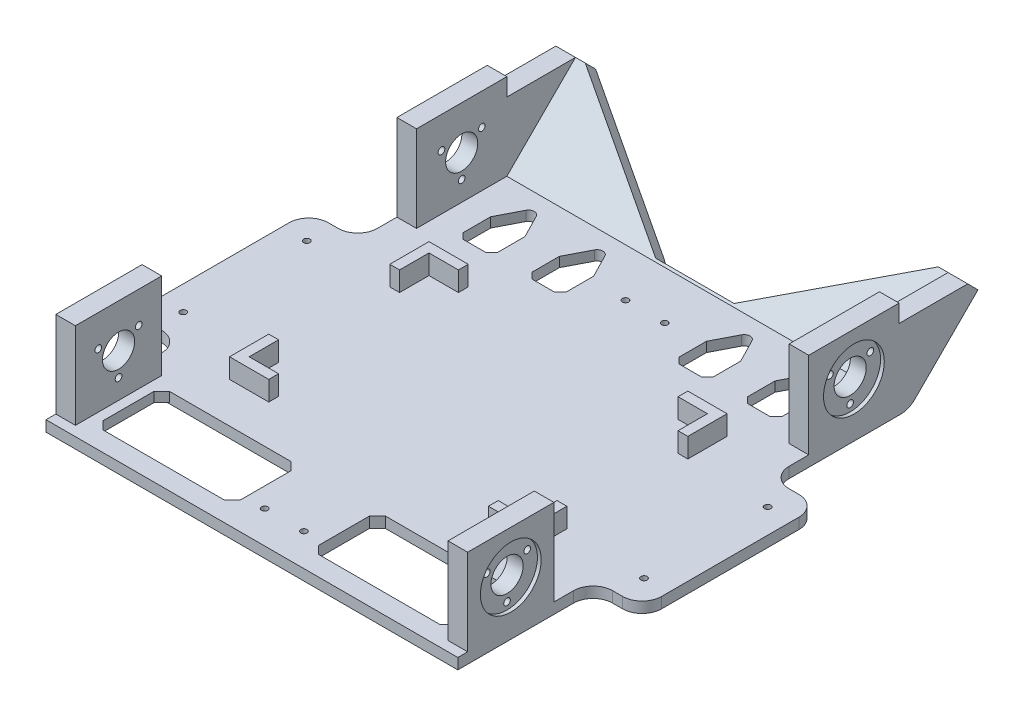
SolidWorks part; units mm, degrees
ref_plane "前视基准面" through (0, 0, 0) normal (0, 0, 1) x (1, 0, 0)
ref_plane "上视基准面" through (0, 0, 0) normal (0, 1, 0) x (1, 0, 0)
ref_plane "右视基准面" through (0, 0, 0) normal (1, 0, 0) x (0, 0, -1)
sketch "草图1" plane through (0, 0, 0) normal (0, 1, 0) x (1, 0, 0)
  line L0 (0, 0) -> (210, 0)
  line L1 (210, 0) -> (210, -230)
  line L2 (210, -230) -> (0, -230)
  line L3 (0, -230) -> (0, 0)
  line L4 (0, 0) -> (3, 0)
  line L5 (0, 0) -> (5, 0)
  line L6 (5, 0) -> (5, -230)
  line L7 (210, 0) -> (205, 0)
  line L8 (205, 0) -> (205, -230)
  line L9 (0, 0) -> (0, -10)
  line L10 (0, -10) -> (210, -10)
  line L11 (210, -230) -> (210, -220)
  line L12 (210, -220) -> (0, -220)
  line L13 (5, -10) -> (85, -10)
  line L14 (85, -10) -> (85, -44)
  line L15 (85, -44) -> (5, -44)
  line L16 (205, -10) -> (125, -10)
  line L17 (125, -10) -> (125, -44)
  line L18 (125, -44) -> (205, -44)
  line L19 (5, -220) -> (5, -186)
  line L20 (5, -186) -> (85, -186)
  line L21 (85, -186) -> (85, -220)
  line L22 (85, -220) -> (5, -220)
  line L23 (205, -220) -> (125, -220)
  line L24 (125, -220) -> (125, -186)
  line L25 (125, -186) -> (205, -186)
  line L26 (205, -186) -> (205, -220)
  line L27 (5, -10) -> (5, -44)
  line L28 (205, -44) -> (205, -10)
extrude "凸台-拉伸1" add sketch "草图1" along normal blind 5.5 contours L24 L25 L8 L18 L17 L10 L14 L15 L6 L20 L21 L12 | L3 L10 L6 L0 | L12 L6 L10 L3 | L6 L10 L8 L0 | L12 L1 L10 L8 | L8 L10 L1 L0 | L8 L12 L6 L2 | L6 L12 L3 L2 | L1 L12 L8 L2 region at (2.5, 0, 5) region at (2.5, 0, 115) region at (105, 0, 5) region at (2.5, 0, 225) region at (207.5, 0, 5) region at (105, 0, 225) region at (105, 0, 115) region at (207.5, 0, 115) region at (207.5, 0, 225)
sketch "草图3" plane through (0, 5.5, 0) normal (0, 1, 0) x (1, 0, 0)
  line L0 (85, -10) -> (85, 0)
  line L1 (0, 0) -> (210, 0) construction
  line L2 (85, 0) -> (85, -5)
  line L3 (85, -5) -> (0, -5)
  line L4 (0, -230) -> (0, 0) construction
  line L5 (0, -5) -> (0, -46.0662)
  line L6 (0, -46.0662) -> (0, -51.0662)
  line L7 (0, -51.0662) -> (5, -51.0662)
  line L8 (5, -51.0662) -> (5, -5)
  line L9 (105, 0) -> (105, -230)
  line L10 (210, -230) -> (0, -230) construction
  line L11 (5, -220) -> (5, -225)
  line L12 (5, -225) -> (0, -225)
  line L13 (0, -225) -> (0, -181)
  line L14 (0, -181) -> (5, -181)
  line L15 (5, -181) -> (5, -220)
  line L16 (210, -181) -> (205, -181)
  line L17 (210, -225) -> (210, -181)
  line L18 (205, -225) -> (210, -225)
  line L19 (205, -220) -> (205, -225)
  line L20 (205, -181) -> (205, -220)
  line L21 (5, -5) -> (5, -51.0662)
  line L22 (0, -51.0662) -> (0, -5)
  line L23 (210, -46.0662) -> (210, -51.0662)
  line L24 (210, -51.0662) -> (205, -51.0662)
  line L25 (205, -51.0662) -> (205, -5)
  line L26 (210, -5) -> (210, -46.0662)
  line L27 (205, -5) -> (210, -5)
extrude "凸台-拉伸2" add sketch "草图3" along normal blind 44 contours L7 L8 L17 L3 L10 | L15 L14 L10 L12 L11 L26 | L16 L20 L6 L19 L18 L2 | L27 L25 L22 L24 L2 region at (2.5, 5.5, 28.0331) region at (2.5, 5.5, 203) region at (207.5, 5.5, 203) region at (207.5, 5.5, 28.0331)
sketch "草图4" plane through (0, 0, 0) normal (-1, 0, 0) x (0, 0, 1)
  line L0 (5, 49.5) -> (51.0662, 5.5)
  line L1 (181, 49.5) -> (225, 5.5)
  circle A1 centre (203, 27.5) radius 17
  circle A2 centre (28.0331, 27.5) radius 15
  circle A3 centre (28.0331, 27.5) radius 8.2
  circle A4 centre (28.0331, 27.5) radius 11.9
  circle A5 centre (28.0331, 15.6) radius 1.7
  circle A6 centre (17.7274, 33.45) radius 1.7
  circle A7 centre (38.3388, 33.45) radius 1.7
  point P24 (28.0331, 27.5)
  dimension "D1" = 3
extrude "切除-拉伸1" cut sketch "草图4" against normal through all both and the other way through all contours A4 A6 | A4 A6 | A4 A7 | A4 A7 | A4 A5 | A4 A5 | L0 A3 | L0 A3 region at (0, 30.0167, 30.4369) region at (0, 24.9833, 25.6293) region at (0, 33.7996, 38.9443) region at (0, 33.0785, 37.6954) region at (0, 33.0785, 18.3708) region at (0, 33.7996, 17.1219) region at (0, 14.9008, 28.0331) region at (0, 16.3429, 28.0331)
sketch "草图5" plane through (0, 0, 0) normal (-1, 0, 0) x (0, 0, 1)
  circle A1 centre (28.0331, 27.5) radius 15.5
extrude "切除-拉伸3" cut sketch "草图5" against normal blind 1.9
sketch "草图6" plane through (210, 0, 0) normal (1, 0, 0) x (0, 0, -1)
  circle A0 centre (-28.0331, 27.5) radius 15.5
extrude "切除-拉伸4" cut sketch "草图6" against normal blind 1.9
sketch "草图7" plane through (0, 0, 0) normal (-1, 0, 0) x (0, 0, 1)
  line L0 (181, 49.5) -> (225, 5.5)
  line L1 (203, 27.5) -> (203, 15.6)
  circle A0 centre (203, 27.5) radius 11.9
  circle A1 centre (203, 27.5) radius 8.2
  circle A2 centre (203, 15.6) radius 1.7
  circle A3 centre (192.6943, 33.45) radius 1.7
  circle A4 centre (213.3057, 33.45) radius 1.7
  point P15 (203, 27.5)
  dimension "D1" = 3
extrude "切除-拉伸5" cut sketch "草图7" against normal through all both and the other way through all contours A0 A3 | A0 A3 | A0 A4 | A0 A4 | A0 A2 L1 | L1 A2 A0 | A0 A2 | L0 A1 | L0 A1 L1 | L1 A1 L0 region at (0, 29.9609, 205.4609) region at (0, 25.8594, 199.0393) region at (0, 33.7996, 213.9112) region at (0, 33.0785, 212.6623) region at (0, 33.0785, 193.3377) region at (0, 33.7996, 192.0888) region at (0, 22.5783, 205.0386) region at (0, 16.3429, 203.7042) region at (0, 16.3429, 202.2958) region at (0, 14.9008, 203)
sketch "草图8" plane through (0, 0, 0) normal (-1, 0, 0) x (0, 0, 1)
  circle A0 centre (203, 27.5) radius 15.5
extrude "切除-拉伸6" cut sketch "草图8" against normal blind 1.9
sketch "草图9" plane through (210, 0, 0) normal (1, 0, 0) x (0, 0, -1)
  circle A0 centre (-203, 27.5) radius 15.5
extrude "切除-拉伸7" cut sketch "草图9" against normal blind 1.9
sketch "草图10" plane through (0, 5.5, 0) normal (0, 1, 0) x (1, 0, 0)
  line L0 (5, -10) -> (15, -10)
  line L1 (5, -10) -> (85, -10) construction
  line L2 (15, -10) -> (15, -220)
  line L3 (85, -220) -> (5, -220) construction
  line L4 (15, -220) -> (5, -220)
  line L5 (5, -220) -> (5, -186)
  line L6 (5, -181) -> (5, -225) construction
  line L7 (5, -181) -> (5, -186) construction
  line L8 (5, -186) -> (15, -186)
  line L9 (5, -186) -> (85, -186) construction
  line L10 (5, -10) -> (5, -44)
  line L11 (5, -44) -> (15, -44)
  line L12 (85, -44) -> (5, -44) construction
  line L13 (205, -10) -> (195, -10)
  line L14 (125, -10) -> (205, -10) construction
  line L15 (195, -10) -> (195, -220)
  line L16 (205, -220) -> (125, -220) construction
  line L17 (195, -220) -> (205, -220)
  line L18 (205, -220) -> (205, -186)
  line L19 (205, -186) -> (195, -186)
  line L20 (125, -186) -> (205, -186) construction
  line L21 (205, -10) -> (205, -44)
  line L22 (205, -44) -> (195, -44)
  line L23 (125, -44) -> (205, -44) construction
  line M7 (5, -10) -> (85, -10)
  line M9 (85, -44) -> (5, -44)
  line M15 (5, -186) -> (85, -186)
  line M17 (85, -220) -> (5, -220)
  line M25 (205, -220) -> (125, -220)
  line M27 (125, -186) -> (205, -186)
  line M33 (205, -44) -> (125, -44)
  line M35 (125, -10) -> (205, -10)
extrude "凸台-拉伸3" add sketch "草图10" against normal blind 5 contours L21 L15 M35 M33 | L10 L2 M7 M9 | L5 L2 M17 M15 | L18 L15 M25 M27 region at (10, 5.5, 203) region at (10, 5.5, 27) region at (200, 5.5, 27) region at (200, 5.5, 203)
sketch "草图11" plane through (0, 5.5, 0) normal (0, 1, 0) x (1, 0, 0)
  line L0 (15, -10) -> (5, -10)
  line L1 (5, -51.0662) -> (5, -5) construction
  line L2 (10, -10) -> (10, -51.0662)
  line L3 (10, -51.0662) -> (5, -51.0662)
  line L4 (5, -51.0662) -> (5, -5)
  line L5 (5, -5) -> (10, -5)
  line L6 (10, -5) -> (10, -10)
  line L7 (10, -51.0662) -> (10, -230)
  line L8 (210, -230) -> (0, -230) construction
  line L9 (5, -225) -> (10, -225)
  line L10 (5, -181) -> (10, -181)
  line L11 (10, -181) -> (10, -225)
  line L12 (5, -181) -> (5, -225)
  line L13 (195, -10) -> (205, -10)
  line L14 (205, -51.0662) -> (205, -5) construction
  line L15 (200, -10) -> (200, -51.0662)
  line L16 (200, -51.0662) -> (205, -51.0662)
  line L17 (205, -51.0662) -> (205, -5)
  line L18 (205, -5) -> (200, -5)
  line L19 (200, -5) -> (200, -10)
  line L20 (200, -225) -> (205, -225)
  line L21 (205, -225) -> (205, -181)
  line L22 (205, -181) -> (200, -181)
  line L23 (200, -181) -> (200, -225)
  line M6 (5, -181) -> (5, -225)
  line M12 (205, -225) -> (205, -181)
  line M16 (205, -51.0662) -> (205, -5)
  line M22 (5, -5) -> (5, -51.0662)
extrude "凸台-拉伸4" add sketch "草图11" along normal blind 44 contours L3 L2 L0 M22 | L6 L5 L0 M22 | L18 L19 L13 M16 | L15 L16 L13 M16 | L10 L9 L7 M6 | L22 L23 L20 M12 region at (7.5, 5.5, 30.5331) region at (7.5, 5.5, 203) region at (7.5, 5.5, 7.5) region at (202.5, 5.5, 7.5) region at (202.5, 5.5, 30.5331) region at (202.5, 5.5, 203)
sketch "草图12" plane through (1.9, 0, 0) normal (-1, 0, 0) x (0, 0, 1)
  circle A0 centre (17.7274, 33.45) radius 1.7
  circle A1 centre (38.3388, 33.45) radius 1.7
  circle A2 centre (28.0331, 15.6) radius 1.7
  circle A3 centre (28.0331, 27.5) radius 8.2
  circle A4 centre (192.6943, 33.45) radius 1.7
  circle A5 centre (213.3057, 33.45) radius 1.7
  circle A6 centre (203, 15.6) radius 1.7
  circle A7 centre (203, 27.5) radius 8.2
extrude "切除-拉伸8" cut sketch "草图12" against normal through all both and the other way through all
sketch "草图13" plane through (210, 0, 0) normal (1, 0, 0) x (0, 0, -1)
  line L0 (-5, 5.5) -> (14.6466, 25.1466)
sketch "草图15" plane through (210, 0, 0) normal (1, 0, 0) x (0, 0, -1)
  line L0 (-5, 5.5) -> (-5, 40.5)
  line L1 (-5, 49.5) -> (-5, 5.5) construction
  line L2 (-5, 40.5) -> (31.0178, 40.5)
ref_plane "基准面5" through (0, 5.25, 5.25) normal (0, 0.7071, 0.7071) x (1, 0, 0)
sketch "草图17" plane through (0, 5.25, 5.25) normal (0, 0.7071, 0.7071) x (1, 0, 0)
  line L0 (210, 0.3536) -> (210, 49.8474)
  line L1 (210, 49.8474) -> (0, 49.8474)
  line L2 (0, 49.8474) -> (0, 0.3536)
  line L3 (0, 0.3536) -> (210, 0.3536)
extrude "凸台-拉伸5" add sketch "草图17" against normal through all
sketch "草图18" plane through (0, 0, 0) normal (-1, 0, 0) x (0, 0, 1)
  line L0 (-29.9975, 40.4975) -> (5, 40.5)
  line L1 (5, 40.5) -> (5, 5.5)
  line L2 (5, 5.5) -> (-29.9975, 40.4975)
extrude "凸台-拉伸6" add sketch "草图18" against normal blind 10
sketch "草图19" plane through (210, 0, 0) normal (1, 0, 0) x (0, 0, -1)
  line L0 (30, 40.5) -> (-5, 40.5)
  line L1 (-5, 40.5) -> (31.0178, 40.5) construction
  line L2 (40.3406, 50.8406) -> (-50.8406, -40.3406) construction
  line L3 (-5, 40.5) -> (-5, 5.5)
  line L4 (-5, 5.5) -> (30, 40.5)
extrude "凸台-拉伸8" add sketch "草图19" against normal blind 10
sketch "草图20" plane through (0, 5.25, 5.25) normal (0, 0.7071, 0.7071) x (1, 0, 0)
  line L0 (15, -3.182) -> (15, 49.8474)
  line L1 (200, 49.8474) -> (10, 49.8474) construction
  line L4 (125, 49.8474) -> (85, 49.8474)
  line L5 (85, 1.6082) -> (125, 1.6082)
  line L6 (125, 1.6082) -> (125, 49.8474)
  line L7 (85, 49.8474) -> (125, 49.8474)
  line L8 (85, 1.6082) -> (85, 49.8474)
  line L9 (15, 49.8474) -> (85, 1.6082)
  line L10 (195, -3.182) -> (195, 49.8474)
  line L11 (195, 49.8474) -> (125, 1.6082)
  line L12 (15, 1.6082) -> (85, 1.6082)
  line L13 (125, 1.6082) -> (195, 1.6082)
  line L14 (195, 1.6082) -> (195, 49.8474)
  line M4 (200, 49.8474) -> (10, 49.8474)
extrude "切除-拉伸9" cut sketch "草图20" against normal blind 10 contours L9 L8 M4 | L8 L5 L6 M4 | L11 L6 M4 region at (61.6667, 29.1274, -18.6274) region at (105, 23.4423, -12.9423) region at (148.3333, 29.1274, -18.6274)
sketch "草图21" plane through (0, 5.5, 0) normal (0, 1, 0) x (1, 0, 0)
  line L1 (15, -10) -> (85, -10) construction
  line L4 (125, -10) -> (195, -10) construction
  line L6 (32.5, -10) -> (15, -44)
  line L7 (32.5, -10) -> (50, -44)
  line L8 (85, -44) -> (15, -44) construction
  line L9 (50, -44) -> (67.5, -10)
  line L10 (67.5, -10) -> (85, -44)
  line L11 (125, -44) -> (142.5, -10)
  line L12 (142.5, -10) -> (160, -44)
  line L14 (160, -44) -> (177.5, -10)
  line L15 (177.5, -10) -> (195, -44)
  line L16 (15, -44) -> (15, -10)
  line L17 (15, -10) -> (32.5, -10)
  line L18 (32.5, -10) -> (67.5, -10)
  line L19 (67.5, -10) -> (85, -10)
  line L20 (85, -10) -> (85, -44)
  line L21 (125, -44) -> (125, -10)
  line L22 (125, -10) -> (142.5, -10)
  line L23 (142.5, -10) -> (177.5, -10)
  line L24 (177.5, -10) -> (195, -10)
  line L25 (195, -10) -> (195, -44)
  line L26 (41.25, -27) -> (41.25, -44)
  line L27 (58.75, -27) -> (58.75, -44)
  line L28 (151.25, -27) -> (151.25, -44)
  line L29 (125, -44) -> (195, -44) construction
  line L30 (168.75, -27) -> (168.75, -44)
  line L31 (41.25, -44) -> (58.75, -44)
  line L32 (151.25, -44) -> (168.75, -44)
  line M21 (15, -44) -> (15, -10)
  line M22 (15, -10) -> (85, -10)
  line M23 (85, -10) -> (85, -44)
  line M24 (85, -44) -> (15, -44)
  line M29 (125, -10) -> (195, -10)
  line M30 (195, -10) -> (195, -44)
  line M31 (195, -44) -> (125, -44)
  line M32 (125, -44) -> (125, -10)
extrude "凸台-拉伸11" add sketch "草图21" against normal blind 5 contours L6 M22 M21 | L7 L9 M22 | L7 L26 M24 | L27 L9 M24 | L10 M22 M23 | L11 M32 M29 | L12 L14 M29 | L15 M29 M30 | L30 L14 M31 | L12 L28 M31 region at (50, 5.5, 21.3333) region at (20.8333, 5.5, 21.3333) region at (44.1667, 5.5, 38.3333) region at (79.1667, 5.5, 21.3333) region at (55.8333, 5.5, 38.3333) region at (130.8333, 5.5, 21.3333) region at (160, 5.5, 21.3333) region at (154.1667, 5.5, 38.3333) region at (189.1667, 5.5, 21.3333) region at (165.8333, 5.5, 38.3333)
sketch "草图22" plane through (0, 0, 0) normal (-1, 0, 0) x (0, 0, 1)
  line L0 (0, 0.5) -> (0, 0)
  line L1 (0, 0) -> (-0.25, 0.25)
  line L2 (-0.25, 0.25) -> (0, 0.5)
extrude "凸台-拉伸13" add sketch "草图22" against normal blind 210
fillet "圆角1" radius 10 1 edges at (105, 0, 0)
sketch "草图23" plane through (0, 5.5, 0) normal (0, 1, 0) x (1, 0, 0)
  line L0 (23.75, -27) -> (23.75, -44)
  line L1 (32.5, -10) -> (15, -44) construction
  line L2 (41.25, -44) -> (15, -44) construction
  line L3 (23.75, -44) -> (15, -44)
  line L4 (15, -44) -> (23.75, -27)
  line L5 (76.25, -27) -> (76.25, -44)
  line L6 (67.5, -10) -> (85, -44) construction
  line L7 (85, -44) -> (58.75, -44) construction
  line L8 (76.25, -44) -> (85, -44)
  line L9 (85, -44) -> (76.25, -27)
  line L10 (133.75, -27) -> (133.75, -44)
  line L11 (125, -44) -> (142.5, -10) construction
  line L12 (125, -44) -> (151.25, -44) construction
  line L13 (133.75, -44) -> (125, -44)
  line L14 (125, -44) -> (133.75, -27)
  line L15 (186.25, -27) -> (186.25, -44)
  line L16 (177.5, -10) -> (195, -44) construction
  line L17 (168.75, -44) -> (195, -44) construction
  line L18 (186.25, -44) -> (195, -44)
  line L19 (195, -44) -> (186.25, -27)
extrude "凸台-拉伸14" add sketch "草图23" against normal blind 5 contours L4 L0 L3 | L9 L5 L8 | L14 L10 L13 | L19 L15 L18
sketch "草图25" plane through (0, 5.5, 0) normal (0, 1, 0) x (1, 0, 0)
  line L0 (105, 21.1547) -> (105, -242.7807) construction
  line L1 (-56.829, -116.0331) -> (264.4539, -116.0331) construction
  line L2 (0, -181) -> (0, -51.0662) construction
  point P8 (0, -116.0331)
sketch "草图26" plane through (0, 5.5, 0) normal (0, 1, 0) x (1, 0, 0)
  line L0 (210, -51.0662) -> (210, -181) construction
  line L1 (210, -161.0331) -> (235, -161.0331)
  line L2 (210, -161.0331) -> (210, -71.0331)
  line L3 (210, -71.0331) -> (235, -71.0331)
  line L4 (235, -161.0331) -> (235, -71.0331)
  line L7 (105, 21.1547) -> (105, -242.7807)
  line L8 (-25, -161.0331) -> (-25, -71.0331)
  line L9 (0, -71.0331) -> (-25, -71.0331)
  line L10 (0, -161.0331) -> (0, -71.0331)
  line L11 (0, -161.0331) -> (-25, -161.0331)
  line L12 (-56.829, -116.0331) -> (264.4539, -116.0331) construction
  dimension "D1" = 25
  dimension "D2" = 90
  dimension "D3" = 45
extrude "凸台-拉伸15" add sketch "草图26" against normal blind 5.5 contours L11 L10 L9 L8 | L1 L4 L3 L2 region at (222.5, 5.5, 116.0331) region at (-12.5, 5.5, 116.0331)
fillet "圆角2" radius 10 8 edges at (210, 2.75, 161.0331) (235, 2.75, 161.0331) (235, 2.75, 71.0331) (210, 2.75, 71.0331) (0, 2.75, 71.0331) (-25, 2.75, 71.0331) (-25, 2.75, 161.0331) (0, 2.75, 161.0331)
chamfer "倒角1" distance 4 angle 45 8 edges at (15, 3, 220) (85, 2.75, 220) (85, 2.75, 186) (15, 3, 186) (125, 2.75, 186) (125, 2.75, 220) (195, 3, 220) (195, 3, 186)
chamfer "倒角2" distance 3 angle 45 8 edges at (41.25, 3, 44) (76.25, 3, 44) (151.25, 3, 44) (168.75, 3, 44) (23.75, 3, 44) (58.75, 3, 44) (133.75, 3, 44) (186.25, 3, 44)
fillet "圆角3" radius 3 4 edges at (177.5, 3, 10) (142.5, 3, 10) (67.5, 3, 10) (32.5, 3, 10)
sketch "草图27" plane through (0, 49.5, 0) normal (0, 1, 0) x (1, 0, 0)
  line L0 (210, -5) -> (200, -5)
  line L1 (200, -5) -> (200, -51.0662)
  line L2 (200, -51.0662) -> (210, -51.0662)
  line L3 (210, -51.0662) -> (210, -5)
  line L4 (200, -181) -> (200, -225)
  line L5 (200, -225) -> (210, -225)
  line L6 (210, -225) -> (210, -181)
  line L7 (210, -181) -> (200, -181)
  line L8 (0, -181) -> (10, -181)
  line L9 (10, -181) -> (10, -225)
  line L10 (10, -225) -> (0, -225)
  line L11 (0, -225) -> (0, -181)
  line L12 (0, -5) -> (10, -5)
  line L13 (10, -5) -> (10, -51.0662)
  line L14 (10, -51.0662) -> (0, -51.0662)
  line L15 (0, -51.0662) -> (0, -5)
sketch "草图28" plane through (0, 5.5, 0) normal (0, 1, 0) x (1, 0, 0)
  line L0 (34, -68.7075) -> (34, -160.4075)
  line L1 (34, -160.4075) -> (176, -160.4075)
  line L2 (176, -160.4075) -> (176, -68.7075)
  line L3 (176, -68.7075) -> (34, -68.7075)
  line L4 (34, -68.7075) -> (34, -83.7075)
  line L5 (34, -83.7075) -> (29, -83.7075)
  line L6 (29, -83.7075) -> (29, -63.7075)
  line L7 (29, -63.7075) -> (49, -63.7075)
  line L8 (49, -63.7075) -> (49, -68.7075)
  line L9 (49, -68.7075) -> (34, -68.7075)
  line L10 (34, -160.4075) -> (34, -145.4075)
  line L11 (34, -145.4075) -> (29, -145.4075)
  line L12 (29, -145.4075) -> (29, -165.4075)
  line L13 (29, -165.4075) -> (49, -165.4075)
  line L14 (49, -165.4075) -> (49, -160.4075)
  line L15 (49, -160.4075) -> (34, -160.4075)
  line L16 (176, -83.7075) -> (181, -83.7075)
  line L17 (181, -83.7075) -> (181, -63.7075)
  line L18 (181, -63.7075) -> (161, -63.7075)
  line L19 (161, -63.7075) -> (161, -68.7075)
  line L20 (161, -68.7075) -> (176, -68.7075)
  line L21 (176, -160.4075) -> (176, -145.4075)
  line L22 (176, -145.4075) -> (181, -145.4075)
  line L23 (181, -145.4075) -> (181, -165.4075)
  line L24 (181, -165.4075) -> (161, -165.4075)
  line L25 (161, -165.4075) -> (161, -160.4075)
  line L26 (161, -160.4075) -> (176, -160.4075)
extrude "凸台-拉伸16" add sketch "草图28" along normal blind 10 contours L8 L7 L6 L5 L0 L3 | L18 L19 L3 L2 L16 L17 | L25 L24 L23 L22 L2 L1 | L10 L11 L12 L13 L14 L15 region at (33.7172, 5.5, 76.2075) region at (161.2828, 5.5, 66.2075) region at (168.5, 5.5, 160.6904)
sketch "草图30" plane through (0, 5.5, 0) normal (0, 1, 0) x (1, 0, 0)
  line L0 (-15, -71.0331) -> (-15, -161.0331)
  line L1 (-10, -71.0331) -> (-15, -71.0331) construction
  line L2 (-15, -161.0331) -> (-10, -161.0331)
  line L3 (-10, -161.0331) -> (-10, -71.0331)
  line L4 (-10, -71.0331) -> (-15, -71.0331)
  line L5 (220, -71.0331) -> (225, -71.0331)
  line L6 (225, -71.0331) -> (225, -161.0331)
  line L7 (225, -161.0331) -> (220, -161.0331)
  line L8 (220, -161.0331) -> (220, -71.0331)
  arc A0 (-15, -71.0331) -> (-25, -81.0331) centre (-15, -81.0331) ccw construction
sketch "草图31" plane through (0, 5.5, 0) normal (0, 1, 0) x (1, 0, 0)
  line L0 (-25, -81.0331) -> (235, -81.0331)
  line L1 (235, -81.0331) -> (235, -151.0331)
  line L2 (235, -151.0331) -> (-25, -151.0331)
  line L3 (-25, -151.0331) -> (-25, -81.0331)
  line L4 (-25, -116.0331) -> (235, -116.0331)
sketch "草图32" plane through (0, 5.5, 0) normal (0, 1, 0) x (1, 0, 0)
  line L0 (76.25, -27) -> (133.75, -27)
  line L1 (133.75, -27) -> (133.75, -41)
  line L2 (133.75, -41) -> (76.25, -41)
  line L3 (76.25, -41) -> (76.25, -27)
  line L4 (85, -216) -> (125, -216)
  line L5 (125, -216) -> (125, -190)
  line L6 (125, -190) -> (85, -190)
  line L7 (85, -190) -> (85, -216)
sketch "草图36" plane through (0, 5.5, 0) normal (0, 1, 0) x (1, 0, 0)
  line L0 (105, 21.1547) -> (105, -242.7807) construction
  line L1 (105, 21.1547) -> (105, -242.7807) construction
  line L2 (220, -71.0331) -> (225, -71.0331) construction
  line L3 (235, -81.0331) -> (235, -151.0331) construction
  line L4 (10, -5) -> (200, -5) construction
  line L5 (115, -29.5) -> (115, -213.6251) construction
  circle A3 centre (115, -213.5) radius 1.6
  circle A4 centre (222.5, -147.5331) radius 1.6
  circle A5 centre (222.5, -84.5331) radius 1.6
  circle A7 centre (115, -29.5) radius 1.6
  circle A8 centre (95, -29.5) radius 1.6
  circle A9 centre (-12.5, -84.5331) radius 1.6
  circle A10 centre (-12.5, -147.5331) radius 1.6
  circle A11 centre (95, -213.5) radius 1.6
  dimension "D1" = 63
  dimension "D2" = 13.5
  dimension "D3" = 3.2
  dimension "D4" = 12.5
  dimension "D5" = 24.5
  dimension "D6" = 10
extrude "切除-拉伸11" cut sketch "草图36" against normal through all
